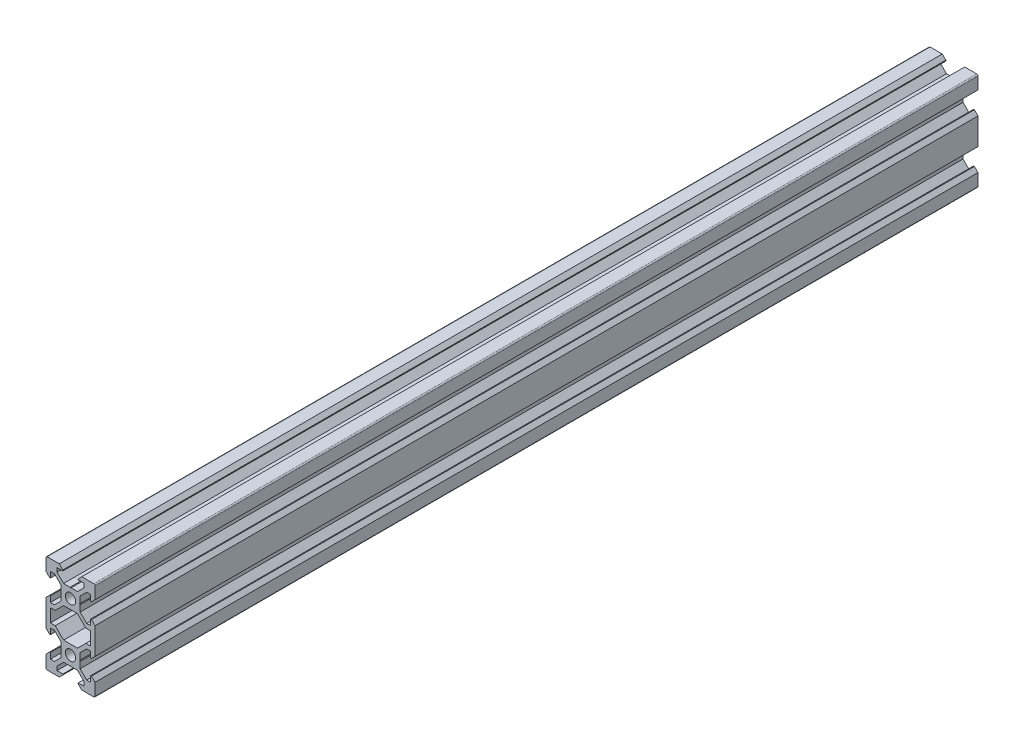
SolidWorks part; units mm, degrees
material "6061-T6 (SS)"
ref_plane "Front Plane" through (0, 0, 0) normal (0, 0, 1) x (1, 0, 0)
ref_plane "Top Plane" through (0, 0, 0) normal (0, 1, 0) x (1, 0, 0)
ref_plane "Right Plane" through (0, 0, 0) normal (1, 0, 0) x (0, 0, -1)
sketch "Sketch1" plane through (0, 0, 0) normal (0, 0, 1) x (1, 0, 0)
  line L0 (0, 0) -> (10, 0) construction
  line L1 (9.5, -20) -> (-9.5, -20)
  line L2 (10, -19.5) -> (10, 19.5)
  line L3 (9.5, 20) -> (-9.5, 20)
  line L4 (-10, -19.5) -> (-10, 19.5)
  line L5 (10, -20) -> (-10, 20) construction
  line L6 (10, 20) -> (-10, -20) construction
  circle A0 centre (0, 10) radius 2.1
  circle A1 centre (0, -10) radius 2.1
  arc A2 (-9.5, -20) -> (-10, -19.5) centre (-9.5, -19.5) cw
  arc A3 (9.5, -20) -> (10, -19.5) centre (9.5, -19.5) ccw
  arc A4 (10, 19.5) -> (9.5, 20) centre (9.5, 19.5) ccw
  arc A5 (-9.5, 20) -> (-10, 19.5) centre (-9.5, 19.5) ccw
  point P0 (0, 0)
  line B0 (0, 10) -> (0, 20) construction
  line B1 (0, 13.69) -> (-0.21, 13.9)
  line B2 (-0.21, 13.9) -> (-2.8393, 13.9)
  line B3 (-2.8393, 13.9) -> (-5.5, 16.5607)
  line B4 (-5.5, 16.5607) -> (-5.5, 18.2)
  line B5 (-5.5, 18.2) -> (-3.125, 18.2)
  line B6 (-3.125, 18.2) -> (-3.125, 18.545)
  line B7 (-3.125, 18.545) -> (-4.58, 20)
  line B8 (-4.58, 20) -> (4.58, 20)
  line B9 (0, 10) -> (-5.9132, 15.9132) construction
  line B10 (3.125, 18.545) -> (4.58, 20)
  line B11 (3.125, 18.2) -> (3.125, 18.545)
  line B12 (5.5, 18.2) -> (3.125, 18.2)
  line B13 (5.5, 16.5607) -> (5.5, 18.2)
  line B14 (2.8393, 13.9) -> (5.5, 16.5607)
  line B15 (0.21, 13.9) -> (2.8393, 13.9)
  line B16 (0, 13.69) -> (0.21, 13.9)
  line B17 (0, 10) -> (-10, 10) construction
  line B18 (-3.69, 10) -> (-3.9, 9.79)
  line B19 (-3.9, 9.79) -> (-3.9, 7.1607)
  line B20 (-3.9, 7.1607) -> (-6.5607, 4.5)
  line B21 (-6.5607, 4.5) -> (-8.2, 4.5)
  line B22 (-8.2, 4.5) -> (-8.2, 6.875)
  line B23 (-8.2, 6.875) -> (-8.545, 6.875)
  line B24 (-8.545, 6.875) -> (-10, 5.42)
  line B25 (-10, 5.42) -> (-10, 14.58)
  line B26 (0, 10) -> (-5.9132, 4.0868) construction
  line B27 (-8.545, 13.125) -> (-10, 14.58)
  line B28 (-8.2, 13.125) -> (-8.545, 13.125)
  line B29 (-8.2, 15.5) -> (-8.2, 13.125)
  line B30 (-6.5607, 15.5) -> (-8.2, 15.5)
  line B31 (-3.9, 12.8393) -> (-6.5607, 15.5)
  line B32 (-3.9, 10.21) -> (-3.9, 12.8393)
  line B33 (-3.69, 10) -> (-3.9, 10.21)
  line B34 (0, -10) -> (-10, -10) construction
  line B35 (-3.69, -10) -> (-3.9, -10.21)
  line B36 (-3.9, -10.21) -> (-3.9, -12.8393)
  line B37 (-3.9, -12.8393) -> (-6.5607, -15.5)
  line B38 (-6.5607, -15.5) -> (-8.2, -15.5)
  line B39 (-8.2, -15.5) -> (-8.2, -13.125)
  line B40 (-8.2, -13.125) -> (-8.545, -13.125)
  line B41 (-8.545, -13.125) -> (-10, -14.58)
  line B42 (-10, -14.58) -> (-10, -5.42)
  line B43 (0, -10) -> (-5.9132, -15.9132) construction
  line B44 (-8.545, -6.875) -> (-10, -5.42)
  line B45 (-8.2, -6.875) -> (-8.545, -6.875)
  line B46 (-8.2, -4.5) -> (-8.2, -6.875)
  line B47 (-6.5607, -4.5) -> (-8.2, -4.5)
  line B48 (-3.9, -7.1607) -> (-6.5607, -4.5)
  line B49 (-3.9, -9.79) -> (-3.9, -7.1607)
  line B50 (-3.69, -10) -> (-3.9, -9.79)
  line B51 (0, -10) -> (0, -20) construction
  line B52 (0, -13.69) -> (0.21, -13.9)
  line B53 (0.21, -13.9) -> (2.8393, -13.9)
  line B54 (2.8393, -13.9) -> (5.5, -16.5607)
  line B55 (5.5, -16.5607) -> (5.5, -18.2)
  line B56 (5.5, -18.2) -> (3.125, -18.2)
  line B57 (3.125, -18.2) -> (3.125, -18.545)
  line B58 (3.125, -18.545) -> (4.58, -20)
  line B59 (4.58, -20) -> (-4.58, -20)
  line B60 (0, -10) -> (5.9132, -15.9132) construction
  line B61 (-3.125, -18.545) -> (-4.58, -20)
  line B62 (-3.125, -18.2) -> (-3.125, -18.545)
  line B63 (-5.5, -18.2) -> (-3.125, -18.2)
  line B64 (-5.5, -16.5607) -> (-5.5, -18.2)
  line B65 (-2.8393, -13.9) -> (-5.5, -16.5607)
  line B66 (-0.21, -13.9) -> (-2.8393, -13.9)
  line B67 (0, -13.69) -> (-0.21, -13.9)
  line B68 (0, -10) -> (10, -10) construction
  line B69 (3.69, -10) -> (3.9, -9.79)
  line B70 (3.9, -9.79) -> (3.9, -7.1607)
  line B71 (3.9, -7.1607) -> (6.5607, -4.5)
  line B72 (6.5607, -4.5) -> (8.2, -4.5)
  line B73 (8.2, -4.5) -> (8.2, -6.875)
  line B74 (8.2, -6.875) -> (8.545, -6.875)
  line B75 (8.545, -6.875) -> (10, -5.42)
  line B76 (10, -5.42) -> (10, -14.58)
  line B77 (0, -10) -> (5.9132, -4.0868) construction
  line B78 (8.545, -13.125) -> (10, -14.58)
  line B79 (8.2, -13.125) -> (8.545, -13.125)
  line B80 (8.2, -15.5) -> (8.2, -13.125)
  line B81 (6.5607, -15.5) -> (8.2, -15.5)
  line B82 (3.9, -12.8393) -> (6.5607, -15.5)
  line B83 (3.9, -10.21) -> (3.9, -12.8393)
  line B84 (3.69, -10) -> (3.9, -10.21)
  line B85 (0, 10) -> (10, 10) construction
  line B86 (3.69, 10) -> (3.9, 10.21)
  line B87 (3.9, 10.21) -> (3.9, 12.8393)
  line B88 (3.9, 12.8393) -> (6.5607, 15.5)
  line B89 (6.5607, 15.5) -> (8.2, 15.5)
  line B90 (8.2, 15.5) -> (8.2, 13.125)
  line B91 (8.2, 13.125) -> (8.545, 13.125)
  line B92 (8.545, 13.125) -> (10, 14.58)
  line B93 (10, 14.58) -> (10, 5.42)
  line B94 (0, 10) -> (5.9132, 15.9132) construction
  line B95 (8.545, 6.875) -> (10, 5.42)
  line B96 (8.2, 6.875) -> (8.545, 6.875)
  line B97 (8.2, 4.5) -> (8.2, 6.875)
  line B98 (6.5607, 4.5) -> (8.2, 4.5)
  line B99 (3.9, 7.1607) -> (6.5607, 4.5)
  line B100 (3.9, 9.79) -> (3.9, 7.1607)
  line B101 (3.69, 10) -> (3.9, 9.79)
  line B102 (-8.2, -2.7) -> (-8.2, 2.7)
  line B103 (-8.2, 2.7) -> (-6.2393, 2.7)
  line B104 (-6.2393, 2.7) -> (-2.8393, 6.1)
  line B105 (-2.8393, 6.1) -> (2.8393, 6.1)
  line B106 (0, 6.1) -> (0, 0) construction
  line B107 (0, 0) -> (-8.2, 0) construction
  line B108 (6.2393, 2.7) -> (2.8393, 6.1)
  line B109 (8.2, 2.7) -> (6.2393, 2.7)
  line B110 (8.2, -2.7) -> (8.2, 2.7)
  line B111 (8.2, -2.7) -> (6.2393, -2.7)
  line B112 (6.2393, -2.7) -> (2.8393, -6.1)
  line B113 (-2.8393, -6.1) -> (2.8393, -6.1)
  line B114 (-6.2393, -2.7) -> (-2.8393, -6.1)
  line B115 (-8.2, -2.7) -> (-6.2393, -2.7)
  line B116 (0, 6.1) -> (0, 10) construction
  line B117 (0, 10) -> (-5.0927, 4.9073) construction
  dimension "D4" = 4.2
  dimension "D5" = 0.5
  dimension "D1" = 20
  dimension "D2" = 40
  dimension "D3" = 20
sketch_block_instance "V Slot 1-4"
sketch_block "V Slot 1" parameters "D1"=10, "D2"=11, "D3"=4.3, "D4"=1.8, "D5"=0.21, "D6"=45, "D7"=9.16, "D8"=1.5, "D9"=6.25
sketch_block_instance "V Slot 1-5"
sketch_block_instance "V Slot 1-6"
sketch_block_instance "V Slot 1-7"
sketch_block_instance "V Slot 1-8"
sketch_block_instance "V Slot 1-9"
sketch_block_instance "Center Cutout 1-1"
sketch_block "Center Cutout 1" parameters "D1"=5.4, "D2"=12.2, "D3"=8.2, "D4"=45, "D5"=10, "D6"=1.5
extrude "Boss-Extrude1" add sketch "Sketch1" along normal blind 360 contours B101 B86 B87 B88 B89 B90 B91 B92 L2 A4 L3 B10 B11 B12 B13 B14 B15 B16 B1 B2 B3 B4 B5 B6 B7 A5 L4 B27 B28 B29 B30 B31 B32 B33 B18 B19 B20 B21 B22 B23 B24 B44 B45 B46 B47 B48 B49 B50 B35 region at (7.04, -19.5528, 0)
ref_plane "Plane1" through (0, 0, 180) normal (0, 0, 1) x (1, 0, 0)
